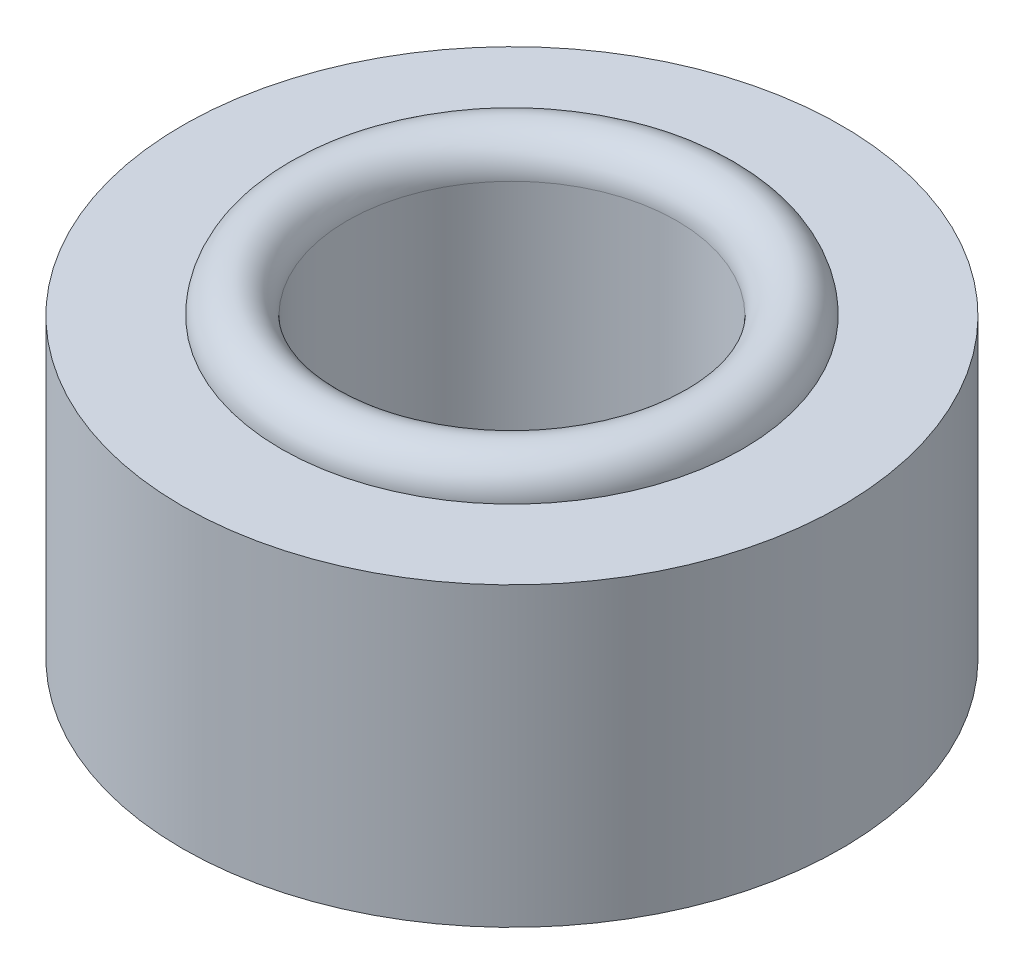
SolidWorks part; units mm, degrees
ref_plane "Front Plane" through (0, 0, 0) normal (0, 0, 1) x (1, 0, 0)
ref_plane "Top Plane" through (0, 0, 0) normal (0, 1, 0) x (1, 0, 0)
ref_plane "Right Plane" through (0, 0, 0) normal (1, 0, 0) x (0, 0, -1)
sketch "Profile Sketch" plane through (0, 0, 0) normal (0, 1, 0) x (1, 0, 0)
  circle A0 centre (0, 0) radius 10
  circle A1 centre (0, 0) radius 5
  dimension "D1" = 20
  dimension "D2" = 10
extrude "Cylinder Extrude" add sketch "Profile Sketch" along normal blind 9
sketch "Lip Ring Sketch" plane through (0, 9, 0) normal (0, 1, 0) x (1, 0, 0)
  circle A0 centre (0, 0) radius 5
  circle A1 centre (0, 0) radius 7
  circle A2 centre (0, 0) radius 5 construction
  dimension "D1" = 2
extrude "Bottom Lip Ring Extrude" add sketch "Lip Ring Sketch" along normal blind 1
fillet "Bottom Ring Fillet" 2 edges at (0, 10, 7) (0, 10, 5) type full round first side face at (0, 10, 7) second side face at (0, 0, 5) middle face at (0, 10, 7)
extrude "Top Lip Ring Extrude" add sketch "Sketch2<2>" against normal blind 1 from surface starting at face at (0, 0, 10)
sketch "Sketch2<2>" plane through (0, 9, 0) normal (0, 1, 0) x (1, 0, 0) same geometry as "Lip Ring Sketch"
fillet "Top Ring Fillet" 2 edges at (0, -1, 7) (0, -1, 5) type full round first side face at (0, -1, 7) second side face at (0, 9, 5) middle face at (0, -1, 5)
